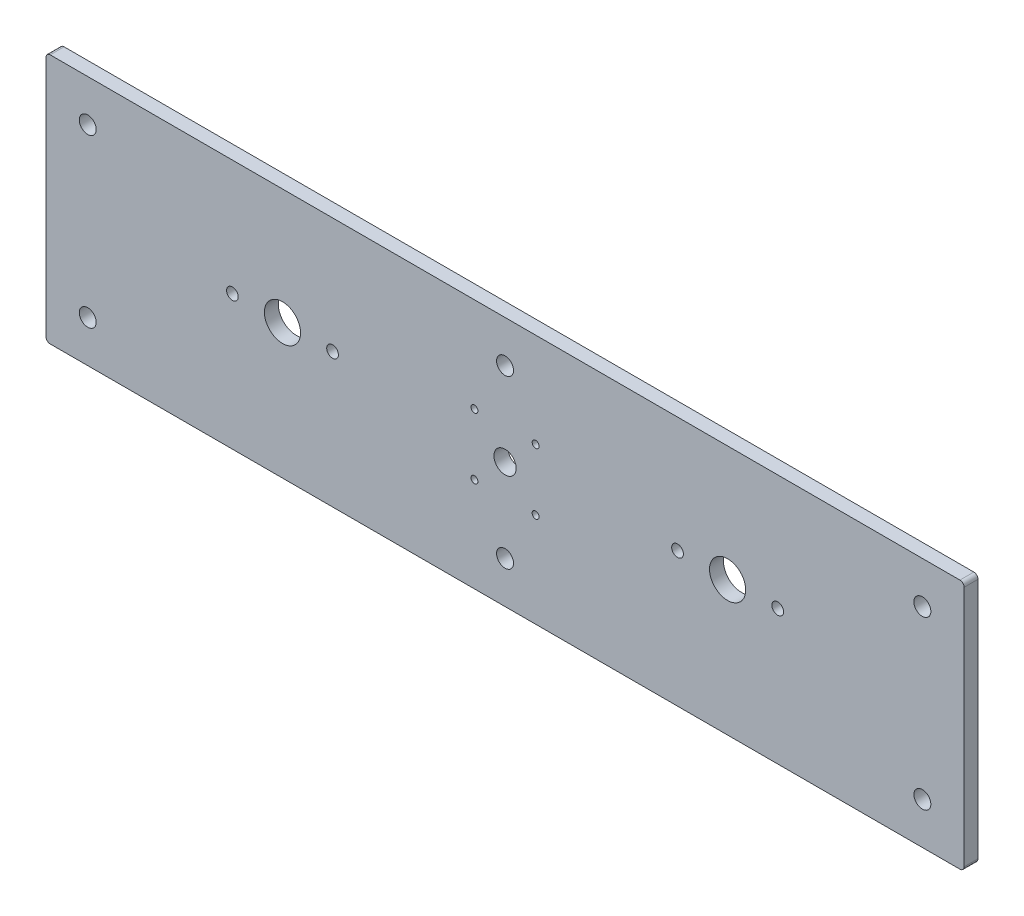
SolidWorks part; units mm, degrees
ref_plane "Front Plane" through (0, 0, 0) normal (0, 0, 1) x (1, 0, 0)
ref_plane "Top Plane" through (0, 0, 0) normal (0, 1, 0) x (1, 0, 0)
ref_plane "Right Plane" through (0, 0, 0) normal (1, 0, 0) x (0, 0, -1)
sketch "Sketch1" plane through (0, 0, 0) normal (0, 0, 1) x (1, 0, 0)
  line L1 (-165, -45) -> (165, -45)
  line L2 (-165, -45) -> (-165, 45)
  line L3 (-165, 45) -> (165, 45)
  line L4 (165, -45) -> (165, 45)
  line L5 (-165, -45) -> (165, 45) construction
  line L6 (-165, 45) -> (165, -45) construction
  point P0 (0, 0)
  dimension "D1" = 330
  dimension "D2" = 90
extrude "Boss-Extrude1" add sketch "Sketch1" along normal mid plane 5
sketch "Sketch2" plane through (0, 0, 2.5) normal (0, 0, 1) x (1, 0, 0)
  line L3 (165, 30) -> (-165, 30)
  line L4 (165, 30) -> (-165, 30) construction
  line L6 (-150, 45) -> (-150, -45)
  line L7 (-150, 45) -> (-150, -45) construction
  line L9 (-165, -30) -> (165, -30)
  line L10 (-165, -30) -> (165, -30) construction
  line L11 (0, 45) -> (0, -45) construction
  line L12 (150, -45) -> (150, 45)
  line L13 (150, -45) -> (150, 45) construction
  line L14 (165, 45) -> (-165, 45) construction
  line L15 (-165, -45) -> (165, -45) construction
  circle A0 centre (150, 30) radius 3.05
  circle A1 centre (150, -30) radius 3.05
  circle A2 centre (0, 30) radius 3.05
  circle A3 centre (0, -30) radius 3.05
  circle A4 centre (-150, -30) radius 3.05
  circle A5 centre (-150, 30) radius 3.05
  dimension "D5" = 6.1
  dimension "D6" = 6.1
  dimension "D7" = 6.1
  dimension "D8" = 6.1
  dimension "D9" = 6.1
  dimension "D10" = 6.1
  dimension "D1" = 15
  dimension "D2" = 15
  dimension "D3" = 15
  dimension "D4" = 15
extrude "Cut-Extrude1" cut sketch "Sketch2" against normal through all
sketch "Sketch3" plane through (0, 0, 2.5) normal (0, 0, 1) x (1, 0, 0)
  line L0 (-165, 3.4) -> (165, 3.4) construction
  circle A0 centre (-80, 3.4) radius 6.5
  circle A1 centre (-62, 3.4) radius 2.1
  circle A2 centre (-98, 3.4) radius 2.1
  dimension "D1" = 13
  dimension "D2" = 4.2
  dimension "D4" = 4.2
  dimension "D7" = 80
  dimension "D3" = 3.4
  dimension "D5" = 18
  dimension "D6" = 18
extrude "Cut-Extrude2" cut sketch "Sketch3" against normal through all
mirror "Mirror1" about plane through (0, 0, 0) normal (1, 0, 0) of "Cut-Extrude2"
sketch "Sketch4" plane through (0, 0, 2.5) normal (0, 0, 1) x (1, 0, 0)
  line L1 (-11, -11) -> (11, -11) construction
  line L2 (-11, -11) -> (-11, 11) construction
  line L3 (-11, 11) -> (11, 11) construction
  line L4 (11, -11) -> (11, 11) construction
  line L5 (-11, -11) -> (11, 11) construction
  line L6 (-11, 11) -> (11, -11) construction
  circle A0 centre (11, 11) radius 1.25
  circle A1 centre (11, -11) radius 1.25
  circle A2 centre (-11, -11) radius 1.25
  circle A3 centre (-11, 11) radius 1.25
  circle A4 centre (0, 0) radius 4
  point P0 (0, 0)
  dimension "D3" = 2.5
  dimension "D4" = 2.5
  dimension "D5" = 2.5
  dimension "D6" = 2.5
  dimension "D7" = 8
  dimension "D1" = 22
  dimension "D2" = 22
extrude "Cut-Extrude3" cut sketch "Sketch4" against normal through all
fillet "Fillet1" radius 1.5 4 edges at (-165, -45, 0) (-165, 45, 0) (165, -45, 0) (165, 45, 0)
equation "\"D8@Sketch2\"=\"D5@Sketch2\""
equation "\"D9@Sketch2\"=\"D5@Sketch2\""
equation "\"D6@Sketch2\"=\"D5@Sketch2\""
equation "\"D7@Sketch2\"=\"D5@Sketch2\""
equation "\"D10@Sketch2\"=\"D5@Sketch2\""
equation "\"D4@Sketch4\"=\"D3@Sketch4\""
equation "\"D6@Sketch4\"=\"D3@Sketch4\""
equation "\"D5@Sketch4\"=\"D3@Sketch4\""
